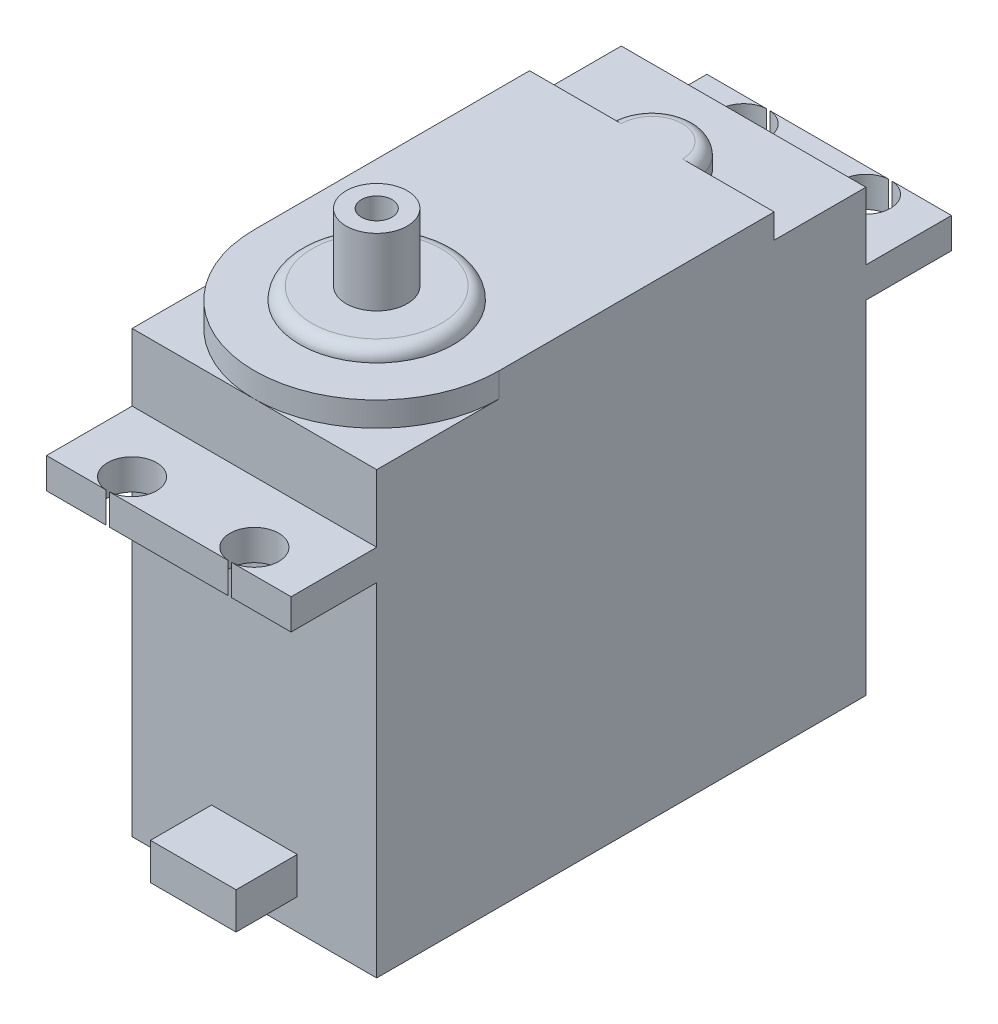
SolidWorks part; units mm, degrees
ref_plane "Front Plane" through (0, 0, 0) normal (0, 0, 1) x (1, 0, 0)
ref_plane "Top Plane" through (0, 0, 0) normal (0, 1, 0) x (1, 0, 0)
ref_plane "Right Plane" through (0, 0, 0) normal (1, 0, 0) x (0, 0, -1)
sketch "Sketch1" plane through (0, 0, 0) normal (0, 1, 0) x (1, 0, 0)
  line L1 (0, 0) -> (20, 0)
  line L2 (0, 0) -> (0, 40)
  line L3 (0, 40) -> (20, 40)
  line L4 (20, 0) -> (20, 40)
  dimension "D1" = 40
  dimension "D2" = 20
extrude "Boss-Extrude1" add sketch "Sketch1" along normal blind 36
sketch "Sketch2" plane through (0, 0, 0) normal (0, 0, 1) x (1, 0, 0)
  line L0 (6.5, 2.5) -> (0, 0) construction
  line L1 (6.5, 2.5) -> (13.5, 2.5)
  line L2 (6.5, 2.5) -> (6.5, 5.5)
  line L3 (6.5, 5.5) -> (13.5, 5.5)
  line L4 (13.5, 2.5) -> (13.5, 5.5)
  line L5 (13.5, 2.5) -> (20, 0) construction
  line L6 (0, 0) -> (20, 0) construction
  dimension "D1" = 7
  dimension "D2" = 3
  dimension "." = 2.5
extrude "Boss-Extrude2" add sketch "Sketch2" along normal blind 5
sketch "Sketch3" plane through (0, 36, 0) normal (0, 1, 0) x (1, 0, 0)
  line L0 (0, 0) -> (20, 0) construction
  line L1 (10, 10) -> (0, 0) construction
  line L2 (10, 10) -> (20, 0) construction
  line L3 (20, 0) -> (20, 40) construction
  circle A0 centre (10, 10) radius 2.5
  dimension "D1" = 10
  dimension "D2" = 5
extrude "Boss-Extrude3" add sketch "Sketch3" along normal blind 8.5
sketch "Sketch4" plane through (0, 0, 0) normal (0, 0, 1) x (1, 0, 0)
  line L0 (0, 36) -> (0, 0) construction
  line L1 (0, 30.5) -> (20, 30.5)
  line L2 (0, 30.5) -> (0, 28)
  line L3 (0, 28) -> (20, 28)
  line L4 (20, 30.5) -> (20, 28)
  line L5 (20, 36) -> (20, 0) construction
  line L7 (0, 0) -> (20, 0) construction
  dimension "D1" = 2.5
  dimension "D2" = 28
extrude "Boss-Extrude4" add sketch "Sketch4" along normal blind 7 and the other way blind 47
sketch "Sketch5" plane through (0, 30.5, 0) normal (0, 1, 0) x (1, 0, 0)
  line L0 (10, -7) -> (10, 47) construction
  line L1 (20, -7) -> (0, -7) construction
  line L2 (20, 47) -> (0, 47) construction
  line L3 (10, 20) -> (15, 20) construction
  line L4 (10, 20) -> (5, 20) construction
  line L5 (15, 20) -> (15, 45.005) construction
  line L6 (15, 20) -> (15, -5.005) construction
  line L7 (15, -5.005) -> (5, -5.005) construction
  line L8 (15, 45.005) -> (5, 45.005) construction
  line L9 (5, 20) -> (5, 45.005) construction
  line L10 (5, 20) -> (5, -5.005) construction
  circle A0 centre (15, 45.005) radius 2
  circle A1 centre (5, 45.005) radius 2
  circle A2 centre (15, -5.005) radius 2
  circle A3 centre (5, -5.005) radius 2
  dimension "D1" = 10
  dimension "D2" = 10
  dimension "D3" = 50.01
extrude "Cut-Extrude1" cut sketch "Sketch5" against normal blind 7
sketch "Sketch6" plane through (0, 36, 0) normal (0, 1, 0) x (1, 0, 0)
  line L0 (20, 0) -> (20, 40) construction
  line L1 (20, 32.5) -> (13.5, 32.5)
  line L2 (20, 32.5) -> (20, 10)
  line L4 (0, 32.5) -> (0, 10)
  line L5 (6.5, 32.5) -> (0, 32.5)
  line L6 (0, 40) -> (0, 0) construction
  line L7 (20, 40) -> (0, 40) construction
  arc A0 (0, 10) -> (20, 10) centre (10, 10) ccw
  circle A1 centre (10, 10) radius 2.5 construction
  arc A2 (13.5, 32.5) -> (6.5, 32.5) centre (10, 32.5) ccw
  dimension "D1" = 3.5
  dimension "D2" = 7.5
extrude "Boss-Extrude5" add sketch "Sketch6" along normal blind 2
sketch "Sketch7" plane through (0, 38, 0) normal (0, 1, 0) x (1, 0, 0)
  circle A0 centre (10, 10) radius 6.2895
  circle A1 centre (10, 10) radius 2.5 construction
extrude "Boss-Extrude6" add sketch "Sketch7" along normal blind 1
fillet "Fillet1" radius 1 1 edges at (10, 39, -3.7105)
fillet "Fillet2" radius 1 1 edges at (10, 38, -36)
sketch "Sketch8" plane through (0, 44.5, 0) normal (0, 1, 0) x (1, 0, 0)
  circle A0 centre (10, 10) radius 1.25
  dimension "D1" = 2.5
extrude "Cut-Extrude2" cut sketch "Sketch8" against normal blind 5
